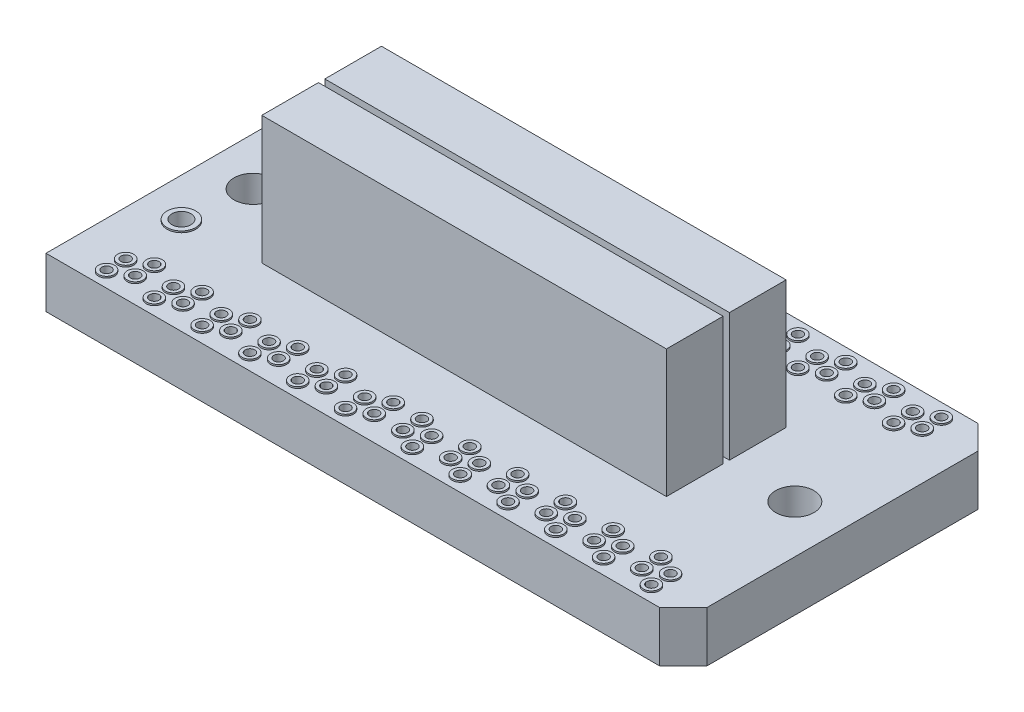
SolidWorks part; units mm, degrees
ref_plane "Front Plane" through (0, 0, 0) normal (0, 0, 1) x (1, 0, 0)
ref_plane "Top Plane" through (0, 0, 0) normal (0, 1, 0) x (1, 0, 0)
ref_plane "Right Plane" through (0, 0, 0) normal (1, 0, 0) x (0, 0, -1)
sketch "Sketch1" plane through (0, 0, 0) normal (0, 1, 0) x (1, 0, 0)
  line L0 (-10, -5) -> (10, -5)
  line L1 (-10, -5) -> (-10, 5)
  line L2 (10, -5) -> (10, 5)
  line L3 (-10, 5) -> (10, 5)
  line L4 (-10, -5) -> (10, 5) construction
  line L5 (10, -5) -> (-10, 5) construction
  point P1 (0, 0)
  dimension "D1" = 20
  dimension "D2" = 10
extrude "PCB" add sketch "Sketch1" along normal blind 1.5875
sketch "Sketch2" plane through (0, 1.5875, 0) normal (0, 1, 0) x (1, 0, 0)
  line L1 (-6.35, -0.1) -> (6.35, -0.1)
  line L2 (-6.35, -0.1) -> (-6.35, -1.878)
  line L3 (-6.35, -1.878) -> (6.35, -1.878)
  line L4 (6.35, -0.1) -> (6.35, -1.878)
  line L10 (0, 0) -> (0, 5.3763) construction
  line L12 (6.35, -0.1) -> (-6.35, -1.878) construction
  point P4 (0, 0)
  point P8 (0, -0.989)
  dimension "D1" = 12.7
  dimension "D2" = 1.778
  dimension "D4" = 0.1
extrude "Connector" add sketch "Sketch2" along normal blind 4.0132
mirror "Mirror1" about plane through (0, 0, 0) normal (0, 0, 1) of "Connector"
sketch "Sketch3" plane through (0, 1.5875, 0) normal (0, 1, 0) x (1, 0, 0)
  line L0 (0, 0) -> (0, -6.2242) construction
  line L1 (-0.45, -3.65) -> (-0.45, -4.25) construction
  line L2 (-1.05, -3.95) -> (-1.05, -4.55) construction
  line L3 (-1.05, -3.95) -> (-0.45, -3.95) construction
  line L4 (-10, -5) -> (10, -5) construction
  circle A0 centre (-0.45, -3.65) radius 0.15
  circle A1 centre (-0.45, -4.25) radius 0.15
  circle A2 centre (-1.05, -3.95) radius 0.15
  circle A3 centre (-1.05, -4.55) radius 0.15
  point P10 (0, 0)
  dimension "D1" = 0.6
  dimension "D2" = 0.3
  dimension "D3" = 0.3
  dimension "D6" = 0.3
  dimension "D7" = 0.3
  dimension "D4" = 0.6
  dimension "D5" = 0.6
  dimension "D8" = 0.45
  dimension "D9" = 0.45
extrude "Cut-Extrude1" cut sketch "Sketch3" against normal through all
sketch "Sketch4" plane through (0, 1.5875, 0) normal (0, 1, 0) x (1, 0, 0)
  circle A0 centre (-0.45, -3.65) radius 0.15 construction
  circle A1 centre (-0.45, -4.25) radius 0.15 construction
  circle A2 centre (-1.05, -4.55) radius 0.15 construction
  circle A3 centre (-1.05, -3.95) radius 0.15 construction
  circle A4 centre (-0.45, -3.65) radius 0.15
  circle A5 centre (-0.45, -4.25) radius 0.15
  circle A6 centre (-1.05, -4.55) radius 0.15
  circle A7 centre (-1.05, -3.95) radius 0.15
  circle A8 centre (-1.05, -4.55) radius 0.25
  circle A9 centre (-0.45, -4.25) radius 0.25
  circle A10 centre (-0.45, -3.65) radius 0.25
  circle A11 centre (-1.05, -3.95) radius 0.25
  dimension "D1" = 0.1
extrude "Boss-Extrude3" add sketch "Sketch4" along normal blind 0.05
sketch "Sketch5" plane through (0, 1.5875, 0) normal (0, 1, 0) x (1, 0, 0)
  line L0 (-10, 5) -> (-10, -5) construction
  line L1 (-10, -5) -> (10, -5) construction
  circle A0 centre (-8.75, -2) radius 0.3
  dimension "D1" = 0.6
  dimension "D2" = 1.25
  dimension "D3" = 3
extrude "Cut-Extrude2" cut sketch "Sketch5" against normal through all
sketch "Sketch6" plane through (0, 1.5875, 0) normal (0, 1, 0) x (1, 0, 0)
  circle A0 centre (-8.75, -2) radius 0.3 construction
  circle A1 centre (-8.75, -2) radius 0.3
  circle A2 centre (-8.75, -2) radius 0.45
  dimension "D1" = 0.15
extrude "Boss-Extrude4" add sketch "Sketch6" along normal blind 0.05
pattern_linear "LPattern1" count 6 spacing 1.5 along (-1, 0, 0) of "Boss-Extrude3", "Cut-Extrude1"
mirror "Mirror2" about plane through (0, 0, 0) normal (1, 0, 0) of "LPattern1"
mirror "Mirror3" about plane through (0, 0, 0) normal (0, 0, 1) of "Boss-Extrude4", "Cut-Extrude2", "Mirror2", "LPattern1"
chamfer "Chamfer1" distance 0.75 angle 45 2 edges at (10, 0.7937, -5) (10, 0.7937, 5)
sketch "Sketch8" plane through (0, 0, -1.878) normal (0, 0, 1) x (1, 0, 0)
  line L0 (-6.35, 2.5875) -> (6.35, 2.5875) construction
  line L3 (-6.35, 1.5875) -> (6.35, 1.5875) construction
  text T0 "OMNETICS" font "Arial" height 1.5
  dimension "D1" = 1
extrude "Boss-Extrude - Label" add sketch "Sketch8" against normal blind 0.01
sketch "Sketch9" plane through (0, 0, 0) normal (0, -1, 0) x (-1, 0, 0)
  circle A0 centre (-8.5, 0) radius 0.6
  circle A1 centre (8.5, 0) radius 0.6
  dimension "D3" = 1.2
  dimension "D4" = 1.2
  dimension "D1" = 8.5
  dimension "D2" = 8.5
extrude "Cut-Extrude - Mounting Holes" cut sketch "Sketch9" against normal blind 10
